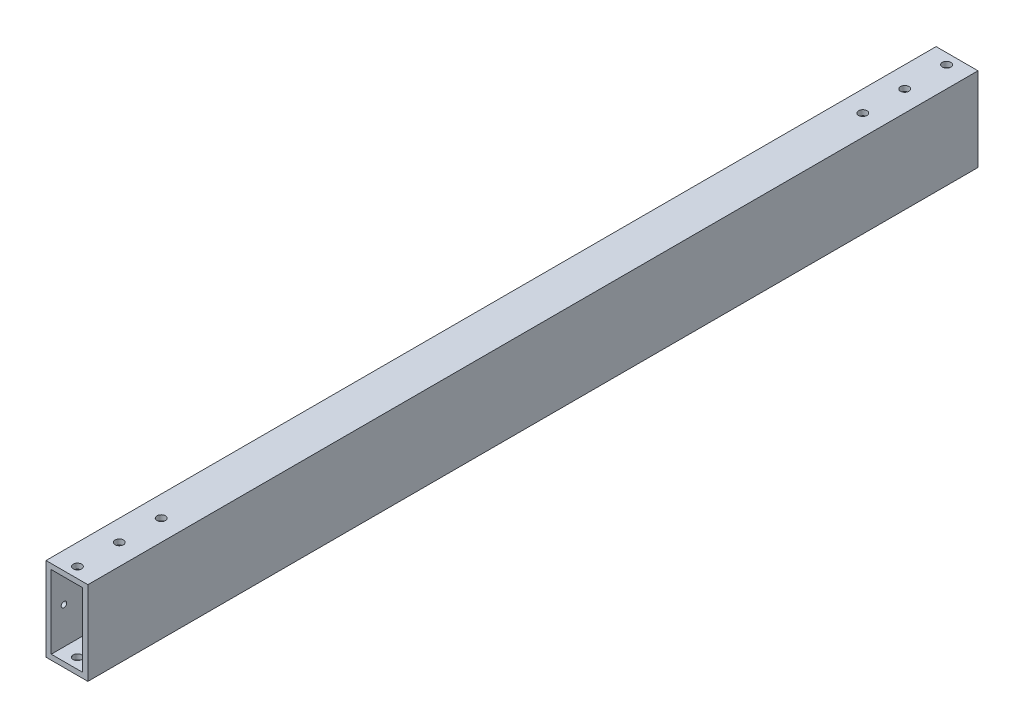
SolidWorks part; units mm, degrees
material "6061-T6 (SS)"
ref_plane "Front" through (0, 0, 0) normal (0, 0, 1) x (1, 0, 0)
ref_plane "Top" through (0, 0, 0) normal (0, 1, 0) x (1, 0, 0)
ref_plane "Right" through (0, 0, 0) normal (1, 0, 0) x (0, 0, -1)
sketch "Sketch1" plane through (0, 0, 0) normal (0, 0, 1) x (1, 0, 0)
  line L1 (-12.7, -25.4) -> (12.7, -25.4)
  line L2 (-12.7, -25.4) -> (-12.7, 25.4)
  line L3 (-12.7, 25.4) -> (12.7, 25.4)
  line L4 (12.7, -25.4) -> (12.7, 25.4)
  line L5 (-12.7, -25.4) -> (12.7, 25.4) construction
  line L6 (-12.7, 25.4) -> (12.7, -25.4) construction
  point P0 (0, 0)
  dimension "D1" = 25.4
  dimension "D2" = 50.8
extrude "Extrude-Thin1" add sketch "Sketch1" along normal blind 539.75 thin thin type one direction reverse wall 3.175
hole_wizard "#10 Clearance Hole1" positions "Sketch2" profile "Sketch3" hole size "#10" standard "ANSI Inch" end condition through all
sketch "Sketch2" plane through (0, 25.4, 0) normal (0, 1, 0) x (1, 0, 0)
  line L0 (-12.7, -539.75) -> (-12.7, 0) construction
  line L1 (12.7, -539.75) -> (-12.7, -539.75) construction
  point P0 (0, -533.4)
  point P2 (0, -508)
  point P4 (0, -482.6)
  point P6 (0, -6.35)
  point P8 (0, -31.75)
  point P10 (0, -57.15)
  dimension "D1" = 12.7
  dimension "D2" = 25.4
  dimension "D3" = 6.35
  dimension "D4" = 25.4
  dimension "D5" = 6.35
  dimension "D6" = 25.4
  dimension "D7" = 25.4
sketch "Sketch3" plane through (0, 25.4, 533.4) normal (1, 0, 0) x (0, 0, 1)
  line L0 (0, 0) -> (0, 50.8)
  line L1 (0, 50.8) -> (2.5527, 50.8)
  line L2 (2.5527, 50.8) -> (2.5527, 0)
  line L5 (2.5527, 0) -> (0, 0)
  line L11 (0, -6.35) -> (0, 107.95) construction
  dimension "Thru Hole Dia." = 5.1054
  dimension "Thru Hole Depth" = 50.8
sketch "Sketch6" plane through (-12.7, 0, 0) normal (-1, 0, 0) x (0, 0, 1)
  point P0 (172.05, 0)
  point P3 (112.05, 0)
  point P6 (52.05, 0)
  point P9 (232.05, 0)
  point P12 (292.05, 0)
  point P15 (352.05, 0)
  point P18 (412.05, 0)
  point P21 (472.05, 0)
  point P24 (532.05, 0)
hole_wizard "M4x0.7 Tapped Hole1" positions "Sketch6" profile "Sketch5" tap size "M4x0.7" standard "ANSI Metric" end condition up to next
cosmetic thread "Hole Thread1" parameters "D2"=4
cosmetic thread "Hole Thread2" parameters "D2"=4
cosmetic thread "Hole Thread3" parameters "D2"=4
cosmetic thread "Hole Thread4" parameters "D2"=4
cosmetic thread "Hole Thread5" parameters "D2"=4
cosmetic thread "Hole Thread6" parameters "D2"=4
cosmetic thread "Hole Thread7" parameters "D2"=4
cosmetic thread "Hole Thread8" parameters "D2"=4
cosmetic thread "Hole Thread9" parameters "D2"=4
sketch "Sketch5" plane through (-12.7, 0, 172.05) normal (0, 1, 0) x (0, 0, 1)
  line L0 (0, 0) -> (0, 3.175)
  line L1 (0, 3.175) -> (1.65, 3.175)
  line L2 (1.65, 3.175) -> (1.65, 0)
  line L5 (1.65, 0) -> (0, 0)
  line L11 (0, -6.35) -> (0, 107.95) construction
  dimension "Thru Tap Drill Dia." = 3.3
  dimension "Thru Tap Drill Depth" = 3.175
